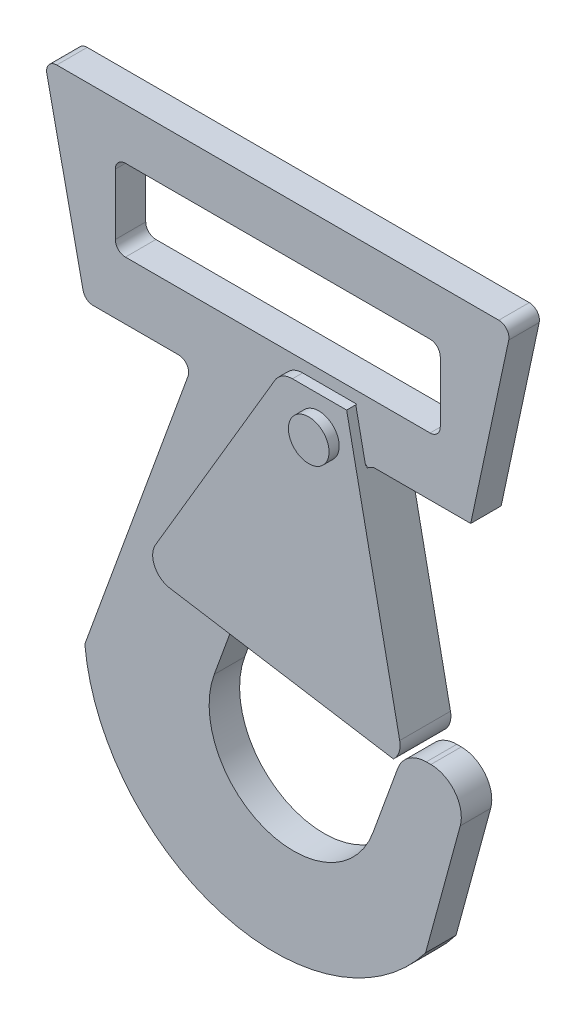
SolidWorks part; units mm, degrees
material "Alloy Steel"
ref_plane "Front Plane" through (0, 0, 0) normal (0, 0, 1) x (1, 0, 0)
ref_plane "Top Plane" through (0, 0, 0) normal (0, 1, 0) x (1, 0, 0)
ref_plane "Right Plane" through (0, 0, 0) normal (1, 0, 0) x (0, 0, -1)
sketch "Sketch1" plane through (0, 0, 0) normal (0, 0, 1) x (1, 0, 0)
  line L0 (-30.1625, 0) -> (30.1625, 0) construction
  line L1 (-30.1625, 0) -> (-30.1625, -26.543)
  line L2 (-30.1625, -26.543) -> (-13.2432, -26.543)
  line L3 (-13.2432, -26.543) -> (-30.1625, -73.0283)
  line L4 (30.1625, 0) -> (30.1625, -26.543)
  line L5 (0, -4.7625) -> (0, 0) construction
  line L6 (30.1625, -26.543) -> (4.7984, -26.543)
  line L7 (4.7984, -26.543) -> (-9.9335, -67.0186)
  line L8 (14.8751, -76.0483) -> (-9.9335, -67.0186) construction
  line L9 (-9.9335, -67.0186) -> (13.8039, -67.0186) construction
  line L10 (14.8751, -76.0483) -> (19.8855, -62.2824)
  line L11 (19.8855, -62.2824) -> (30.1625, -62.2824)
  line L12 (30.1625, -62.2824) -> (23.1042, -88.1967)
  line L14 (-25.4, -4.7625) -> (25.4, -4.7625)
  line L15 (-25.4, -4.7625) -> (-25.4, -17.4625)
  line L16 (-25.4, -17.4625) -> (25.4, -17.4625)
  line L17 (25.4, -4.7625) -> (25.4, -17.4625)
  line L18 (-30.1625, 3.175) -> (30.1625, 3.175)
  line L19 (-30.1625, 0) -> (-30.1625, 3.175)
  line L20 (30.1625, 0) -> (30.1625, 3.175)
  arc A0 (-9.9335, -67.0186) -> (14.8751, -76.0483) centre (2.4708, -71.5335) ccw
  arc A1 (-30.1625, -73.0283) -> (23.1042, -88.1967) centre (-0.5634, -70.1979) ccw
  point P3 (0, 0)
  dimension "D1" = 60.325
  dimension "D2" = 20
  dimension "D4" = 4.7625
  dimension "D3" = 50.8
  dimension "D5" = 12.7
  dimension "D7" = 29.718
  dimension "D6" = 3.175
extrude "Boss-Extrude1" add sketch "Sketch1" along normal mid plane 4.7625 contours L12 L11 L10 A0 L7 L6 L4 L0 L1 L2 L3 L17 region at (-3.2422, -47.7014, 0)
sketch "Sketch2" plane through (0, 0, 2.3813) normal (0, 0, 1) x (1, 0, 0)
  line L0 (2.0709, -19.295) -> (-19.8903, -56.4796)
  line L1 (-19.8903, -56.4796) -> (19.6693, -62.8763)
  line L2 (19.6693, -62.8763) -> (10.7677, -19.295)
  line L3 (2.0709, -19.295) -> (10.7677, -19.295)
  line L4 (6.4193, -19.295) -> (-0.1105, -59.6779) construction
  line L6 (14.8751, -76.0483) -> (19.8855, -62.2824) construction
extrude "Boss-Extrude2" add sketch "Sketch2" along normal blind 1.5875 separate body
mirror "Mirror1" about plane through (0, 0, 0) normal (0, 0, 1) of bodies 102
sketch "Sketch3" plane through (6.5533, 1.3385, 0) normal (0.9798, 0.2001, 0) x (0, 0, -1)
  line L1 (-3.9688, -21.0595) -> (3.9687, -21.0595)
  line L2 (-3.9688, -21.0595) -> (-3.9687, -65.5406)
  line L3 (-3.9687, -65.5406) -> (3.9688, -65.5406)
  line L4 (3.9687, -21.0595) -> (3.9688, -65.5406)
extrude "Boss-Extrude3" add sketch "Sketch3" along direction (-1, 0, 0) on the side of the normal blind 1.5875
fillet "Fillet1" radius 3.175 5 edges at (-19.8903, -56.4796, -3.175) (21.2568, -62.8763, 0) (-19.8903, -56.4796, 3.175) (2.0709, -19.295, -3.175) (2.0709, -19.295, 3.175)
sketch "Sketch4" plane through (8.0772, 1.6498, 0) normal (0.9798, 0.2001, 0) x (0, 0, -1)
  line L0 (3.9687, -21.3772) -> (-3.9688, -21.3772) construction
  line L1 (-2.54, -21.3772) -> (2.54, -21.3772)
  line L2 (-2.54, -21.3772) -> (-2.54, -28.9972)
  line L3 (-2.54, -28.9972) -> (2.54, -28.9972)
  line L4 (2.54, -21.3772) -> (2.54, -28.9972)
  line L5 (0, -21.3772) -> (0, -28.9972) construction
  dimension "D1" = 5.08
  dimension "D2" = 7.62
extrude "Cut-Extrude1" cut sketch "Sketch4" against normal blind 1.5875
sketch "Sketch5" plane through (0, 0, 3.9687) normal (0, 0, 1) x (1, 0, 0)
  circle A0 centre (8.0128, -24.7572) radius 3.175
  dimension "D1" = 6.35
extrude "Boss-Extrude4" add sketch "Sketch5" along normal blind 1.5875 separate body
mirror "Mirror2" about plane through (0, 0, 0) normal (0, 0, 1) of bodies 107
sketch "Sketch6" plane through (0, 0, 2.3813) normal (0, 0, 1) x (1, 0, 0)
  line L0 (14.9584, -26.543) -> (2.1922, -33.7035)
  line L2 (4.7984, -26.543) -> (-9.9335, -67.0186) construction
  line L3 (2.1922, -33.7035) -> (4.7984, -26.543)
  line L4 (4.7984, -26.543) -> (14.9584, -26.543)
  dimension "D1" = 7.62
  dimension "D2" = 10.16
extrude "Boss-Extrude5" add sketch "Sketch6" against normal up to surface (4.7625 mm away) up to face at (0, -11.1125, -2.3813)
fillet "Fillet5" radius 1.5875 4 edges at (25.4, -4.7625, 0) (25.4, -17.4625, 0) (-25.4, -17.4625, 0) (-25.4, -4.7625, 0)
sketch "Sketch7" plane through (0, 0, 2.3813) normal (0, 0, 1) x (1, 0, 0)
  line L0 (-30.1625, -26.543) -> (-36.5125, 3.175)
  line L1 (-36.5125, 3.175) -> (-30.1625, 3.175)
  line L2 (-30.1625, 3.175) -> (-30.1625, -26.543)
  dimension "D1" = 6.35
extrude "Boss-Extrude6" add sketch "Sketch7" against normal up to surface (4.7625 mm away) separate body up to face at (3.242, -45.613, -2.3813)
mirror "Mirror3" about plane through (0, 0, 0) normal (1, 0, 0) of bodies 110
combine bodies "Combine1" operation type add bodies to combine 109 111 110
fillet "Fillet6" radius 1.5875 4 edges at (36.5125, 3.175, 0) (-13.2432, -26.543, 0) (-30.1625, -26.543, 0) (-36.5125, 3.175, 0)
fillet "Fillet7" radius 4.7625 2 edges at (30.1625, -62.2824, 0) (19.8855, -62.2824, 0)
